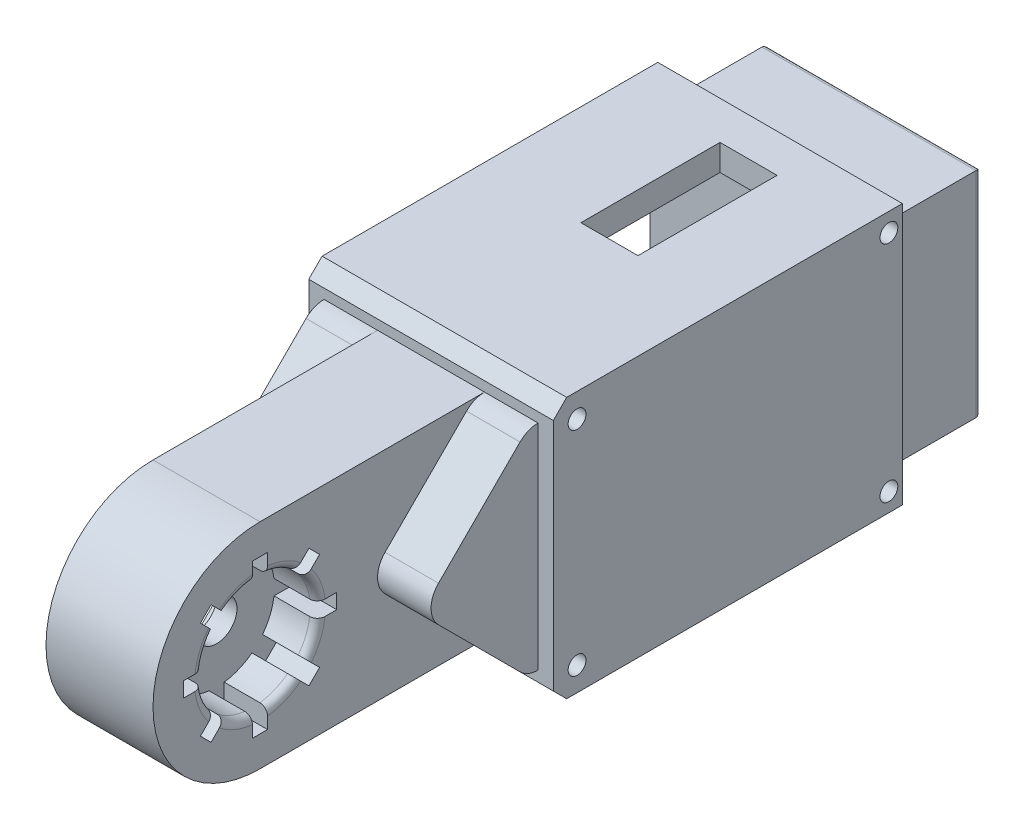
SolidWorks part; units mm, degrees
ref_plane "Front Plane" through (0, 0, 0) normal (0, 0, 1) x (1, 0, 0)
ref_plane "Top Plane" through (0, 0, 0) normal (0, 1, 0) x (1, 0, 0)
ref_plane "Right Plane" through (0, 0, 0) normal (1, 0, 0) x (0, 0, -1)
sketch "Sketch2" plane through (0, 0, 0) normal (0, 0, 1) x (1, 0, 0)
  line L1 (-21, 21) -> (21, 21)
  line L2 (-21, 21) -> (-21, -21)
  line L3 (-21, -21) -> (21, -21)
  line L4 (21, 21) -> (21, -21)
  line L5 (-21, 21) -> (21, -21) construction
  line L6 (-21, -21) -> (21, 21) construction
  point P0 (0, 0)
  dimension "D1" = 42
  dimension "D2" = 42
extrude "Boss-Extrude1" add sketch "Sketch2" along normal blind 89
ref_plane "Plane1" through (0, 0, 89) normal (0, 0, 1) x (1, 0, 0)
sketch "Sketch3" plane through (0, 0, 89) normal (0, 0, 1) x (1, 0, 0)
  line L0 (21, 21) -> (-21, 21) construction
  line L1 (10.5, -21) -> (-10.5, -21)
  line L2 (10.5, -21) -> (10.5, 21)
  line L3 (10.5, 21) -> (-10.5, 21)
  line L4 (-10.5, -21) -> (-10.5, 21)
  line L5 (10.5, -21) -> (-10.5, 21) construction
  line L6 (10.5, 21) -> (-10.5, -21) construction
  point P0 (0, 0)
  dimension "D1" = 21
ref_plane "Plane4" through (0, 0, 0) normal (0, 0, -1) x (-1, 0, 0)
extrude "Boss-Extrude2" add sketch "Sketch3" along normal blind 42
ref_plane "Plane5" through (-10.5, 0, 0) normal (-1, 0, 0) x (0, 0, 1)
sketch "Sketch8" plane through (-10.5, 0, 0) normal (-1, 0, 0) x (0, 0, 1)
  line L0 (131, 21) -> (131, -21) construction
  line L1 (131, 21) -> (131, -21)
  arc A0 (131, 21) -> (131, -21) centre (131, 0) cw
  dimension "D1" = 21
extrude "Boss-Extrude3" add sketch "Sketch8" against normal blind 21
ref_plane "Plane6" through (-10.5, 0, 0) normal (-1, 0, 0) x (0, 0, 1)
sketch "Sketch9" plane through (-10.5, 0, 0) normal (-1, 0, 0) x (0, 0, 1)
  line L0 (89, 21) -> (89, -21) construction
  line L1 (131, 21) -> (131, -21)
  circle A0 centre (131, 0) radius 11.35
  dimension "D1" = 42
  dimension "D2" = 22.7
extrude "Cut-Extrude2" cut sketch "Sketch9" against normal blind 8.5 contours A0
ref_plane "Plane7" through (10.5, 0, 0) normal (1, 0, 0) x (0, 0, -1)
sketch "Sketch11" plane through (10.5, 0, 0) normal (1, 0, 0) x (0, 0, -1)
  line L0 (-131, 21) -> (-131, -21)
  circle A0 centre (-131, 0) radius 11.35
  dimension "D1" = 22.7
extrude "Cut-Extrude3" cut sketch "Sketch11" against normal blind 8.5 contours A0
ref_plane "Plane8" through (-2, 0, 0) normal (-1, 0, 0) x (0, 0, 1)
sketch "Sketch12" plane through (-2, 0, 0) normal (-1, 0, 0) x (0, 0, 1)
  circle A0 centre (131, 0) radius 3.975
  dimension "D1" = 7.95
extrude "Cut-Extrude4" cut sketch "Sketch12" against normal through all
ref_plane "Plane10" through (-2, 0, 0) normal (-1, 0, 0) x (0, 0, 1)
ref_plane "Plane11" through (-10.5, 0, 0) normal (-1, 0, 0) x (0, 0, 1)
sketch "Sketch20" plane through (-10.5, 0, 0) normal (-1, 0, 0) x (0, 0, 1)
  line L0 (131, 0) -> (110, 0)
  line L1 (110, 0) -> (110, 21)
  line L2 (110, 0) -> (110, -21)
  line L4 (110, 21) -> (89, 21)
  line L6 (110, -21) -> (89, -21)
  line L7 (89, 21) -> (110, 0)
  line L8 (89, -21) -> (110, 0)
  line L9 (89, 21) -> (89, -21)
  circle A0 centre (131, 0) radius 11.35
  dimension "D1" = 21
extrude "Boss-Extrude4" add sketch "Sketch20" along normal blind 10.5 and the other way blind 31.5 contours L7 L9 L8 region at (-10.5, 0, 96)
fillet "Fillet1" radius 5 1 edges at (15.75, 0, 110)
fillet "Fillet2" radius 5 1 edges at (-15.75, 0, 110)
fillet "Fillet3" radius 5 1 edges at (-15.75, -21, 89)
fillet "Fillet4" radius 5 1 edges at (-15.75, 21, 89)
fillet "Fillet5" radius 5 1 edges at (15.75, -21, 89)
fillet "Fillet6" radius 5 1 edges at (15.75, 21, 89)
fillet "Fillet7" radius 1.5 1 edges at (-10.5, 0, 142.35)
fillet "Fillet8" radius 1.5 1 edges at (10.5, 0, 119.65)
sketch "Sketch21" plane through (-10.5, 0, 0) normal (-1, 0, 0) x (0, 0, 1)
  line L1 (129.5207, 10.6415) -> (132.4793, 10.6415)
  line L2 (129.5207, 10.6415) -> (129.5207, 15.0585)
  line L3 (129.5207, 15.0585) -> (132.4793, 15.0585)
  line L4 (132.4793, 10.6415) -> (132.4793, 15.0585)
  line L5 (129.5207, 10.6415) -> (132.4793, 15.0585) construction
  line L6 (129.5207, 15.0585) -> (132.4793, 10.6415) construction
  circle A0 centre (131, 0) radius 12.85 construction
  point P0 (131, 12.85)
  dimension "D1" = 4.417
extrude "Cut-Extrude5" cut sketch "Sketch21" against normal blind 8.5
pattern_circular "CirPattern2" count 8 over 360 about axis through (-9, 0, 131) along (-1, 0, 0) of "Cut-Extrude5"
ref_plane "Plane12" through (0, 21, 0) normal (0, 1, 0) x (1, 0, 0)
ref_plane "Plane13" through (10.5, 0, 0) normal (1, 0, 0) x (0, 0, -1)
ref_plane "Plane14" through (0, 0, 0) normal (1, 0, 0) x (0, 0, -1)
mirror "Mirror1" about plane through (0, 0, 0) normal (1, 0, 0) of "CirPattern2"
ref_plane "Plane15" through (21, 0, 0) normal (1, 0, 0) x (0, 0, -1)
sketch "Sketch24" plane through (21, 0, 0) normal (1, 0, 0) x (0, 0, -1)
  line L1 (-86.9289, 21) -> (0, 21)
  line L2 (-86.9289, 21) -> (-86.9289, 25.5452)
  line L3 (-86.9289, 25.5452) -> (0, 25.5452)
  line L4 (0, 21) -> (0, 25.5452)
  line L5 (-86.9289, -21) -> (0, -21)
  line L6 (-86.9289, -21) -> (-86.9289, -25.6891)
  line L7 (-86.9289, -25.6891) -> (0, -25.6891)
  line L8 (0, -21) -> (0, -25.6891)
extrude "Boss-Extrude6" add sketch "Sketch24" against normal blind 42
sketch "Sketch25" plane through (21, 0, 0) normal (1, 0, 0) x (0, 0, -1)
  line L0 (-18.4289, -25.6891) -> (-18.4289, 25.5452)
  line L1 (-86.9289, 25.5452) -> (-18.4289, 25.5452)
  line L2 (-86.9289, 25.5452) -> (-86.9289, -25.6891)
  line L3 (-86.9289, -25.6891) -> (-18.4289, -25.6891)
  dimension "D1" = 68.5
extrude "Boss-Extrude7" add sketch "Sketch25" along normal blind 3
ref_plane "Plane18" through (0, 0, 0) normal (0, 0, -1) x (-1, 0, 0)
ref_plane "Plane19" through (-21, 0, 0) normal (-1, 0, 0) x (0, 0, 1)
sketch "Sketch28" plane through (-21, 0, 0) normal (-1, 0, 0) x (0, 0, 1)
  line L0 (86.9289, -25.6891) -> (0, -25.6891) construction
  line L1 (86.9289, 25.5452) -> (18.4289, 25.5452)
  line L2 (86.9289, 25.5452) -> (86.9289, -25.6891)
  line L3 (86.9289, -25.6891) -> (18.4289, -25.6891)
  line L4 (18.4289, 25.5452) -> (18.4289, -25.6891)
  dimension "D1" = 68.5
extrude "Boss-Extrude8" add sketch "Sketch28" along normal blind 3
ref_plane "Plane20" through (-24, 0, 0) normal (-1, 0, 0) x (0, 0, 1)
sketch "Sketch30" plane through (-24, 0, 0) normal (-1, 0, 0) x (0, 0, 1)
  line L1 (81.9289, 20.4302) -> (19.9289, 20.4302)
  line L2 (81.9289, 20.4302) -> (81.9289, -20.5741)
  line L3 (81.9289, -20.5741) -> (19.9289, -20.5741)
  line L4 (19.9289, 20.4302) -> (19.9289, -20.5741)
  line L5 (81.9289, 20.4302) -> (19.9289, -20.5741) construction
  line L6 (81.9289, -20.5741) -> (19.9289, 20.4302) construction
  line L8 (86.9289, 25.5452) -> (18.4289, 25.5452) construction
  line L9 (18.4289, -25.6891) -> (86.9289, -25.6891) construction
  line L10 (86.9289, -21) -> (86.9289, 21) construction
  point P0 (50.9289, -0.0719)
  dimension "D1" = 5.115
  dimension "D2" = 5.115
  dimension "D3" = 62
  dimension "D4" = 5
extrude "Cut-Extrude6" cut sketch "Sketch30" against normal blind 45
ref_plane "Plane21" through (21, 0, 0) normal (1, 0, 0) x (0, 0, -1)
sketch "Sketch31" plane through (21, 0, 0) normal (1, 0, 0) x (0, 0, -1)
  line L0 (0, -25.6891) -> (0, 25.5452) construction
  line L1 (-18.4289, -25.6891) -> (0, -25.6891)
  line L2 (-18.4289, -25.6891) -> (-18.4289, -21.0741)
  line L3 (-18.4289, -21.0741) -> (0, -21.0741)
  line L4 (0, -25.6891) -> (0, -21.0741)
  line L6 (-18.4289, 25.5452) -> (0, 25.5452)
  line L7 (-18.4289, 25.5452) -> (-18.4289, 20.9302)
  line L8 (-18.4289, 20.9302) -> (0, 20.9302)
  line L9 (0, 25.5452) -> (0, 20.9302)
  dimension "D1" = 4.615
  dimension "D2" = 4.615
extrude "Cut-Extrude7" cut sketch "Sketch31" against normal through all
chamfer "Chamfer1" distance 1.5 angle 45 4 edges at (0, 20.9302, 18.4289) (21, -0.0719, 18.4289) (0, -21.0741, 18.4289) (-21, -0.0719, 18.4289)
ref_plane "Plane22" through (0, 0, 0) normal (0, 0, -1) x (-1, 0, 0)
sketch "Sketch32" plane through (0, 0, 0) normal (0, 0, -1) x (-1, 0, 0)
  line L1 (15, 15) -> (-15, 15)
  line L2 (15, 15) -> (15, -15)
  line L3 (15, -15) -> (-15, -15)
  line L4 (-15, 15) -> (-15, -15)
  line L5 (15, 15) -> (-15, -15) construction
  line L6 (15, -15) -> (-15, 15) construction
  point P0 (0, 0)
  dimension "D1" = 30
  dimension "D2" = 30
extrude "Cut-Extrude8" cut sketch "Sketch32" against normal blind 16.8
ref_plane "Plane23" through (0, 0, 19.9289) normal (0, 0, 1) x (1, 0, 0)
sketch "Sketch33" plane through (0, 0, 19.9289) normal (0, 0, 1) x (1, 0, 0)
  circle A0 centre (0, 0) radius 5
  dimension "D1" = 10
extrude "Cut-Extrude9" cut sketch "Sketch33" against normal blind 16.8
ref_plane "Plane24" through (-21, 0, 0) normal (-1, 0, 0) x (0, 0, 1)
sketch "Sketch34" plane through (-24, 0, 0) normal (-1, 0, 0) x (0, 0, 1)
  line L0 (86.9289, -0.0719) -> (103.6427, -0.0719) construction
  line L2 (88.3304, -21.6696) -> (88.3304, -28.2221)
  line L3 (88.3304, -28.2221) -> (81.7779, -28.2221)
  line L4 (81.7779, -28.2221) -> (88.3304, -21.6696)
  line L5 (86.9289, -25.6891) -> (86.9289, 25.5452) construction
  line L6 (88.3304, 28.0782) -> (81.7779, 28.0782)
  line L7 (88.3304, 21.5257) -> (88.3304, 28.0782)
  line L8 (81.7779, 28.0782) -> (88.3304, 21.5257)
extrude "Cut-Extrude10" cut sketch "Sketch34" against normal through all
chamfer "Chamfer2" distance 6 angle 45 1 edges at (-1.5, 20.4302, 81.9289)
chamfer "Chamfer3" distance 6 angle 45 1 edges at (-1.5, -20.5741, 81.9289)
chamfer "Chamfer4" distance 6 angle 45 1 edges at (-1.5, 20.4302, 19.9289)
chamfer "Chamfer5" distance 6 angle 45 1 edges at (-1.5, -20.5741, 19.9289)
sketch "Sketch35" plane through (-24, 0, 0) normal (-1, 0, 0) x (0, 0, 1)
  line L0 (78.9289, -17.5741) -> (85.6199, -24.3801) construction
  line L1 (82.2744, 20.8332) -> (85.6199, 24.2362) construction
  line L2 (81.9289, -14.5741) -> (75.9289, -20.5741) construction
  line L3 (84.3109, -25.6891) -> (86.9289, -23.0711) construction
  line L4 (78.9289, 17.4302) -> (85.6199, 24.2362) construction
  line L5 (75.9289, 20.4302) -> (81.9289, 14.4302) construction
  line L6 (86.9289, 22.9272) -> (84.3109, 25.5452) construction
  line L7 (18.4289, 25.5452) -> (21.0741, 21.9048) construction
  line L9 (18.4289, -25.6891) -> (21.074, -22.0485) construction
  line L10 (18.4289, 25.5452) -> (18.4289, -25.6891) construction
  circle A0 centre (21.0741, 21.9048) radius 1.75
  circle A1 centre (82.2744, 20.8332) radius 1.75
  circle A2 centre (82.2744, -20.9771) radius 1.75
  circle A3 centre (21.074, -22.0485) radius 1.75
  dimension "D5" = 3.5
  dimension "D1" = 36.003
  dimension "D2" = 36
  dimension "D3" = 4.5
  dimension "D4" = 4.5
extrude "Cut-Extrude11" cut sketch "Sketch35" against normal through all
ref_plane "Plane26" through (0, -25.6891, 0) normal (0, -1, 0) x (-1, 0, 0)
sketch "Sketch38" plane through (0, -25.6891, 0) normal (0, -1, 0) x (-1, 0, 0)
  line L0 (-24, -18.4289) -> (24, -18.4289) construction
  line L1 (4.2922, -53.2289) -> (-6.9078, -53.2289)
  line L2 (4.2922, -53.2289) -> (4.2922, -25.9289)
  line L3 (4.2922, -25.9289) -> (-6.9078, -25.9289)
  line L4 (-6.9078, -53.2289) -> (-6.9078, -25.9289)
  dimension "D1" = 7.5
  dimension "D2" = 27.3
  dimension "D3" = 11.2
extrude "Cut-Extrude12" cut sketch "Sketch38" against normal through all
fillet "Fillet9" radius 1 4 edges at (21, -0.0719, 0) (0, 20.9302, 0) (0, -21.0741, 0) (-21, -0.0719, 0)
fillet "Fillet10" radius 1 4 edges at (0, 15, 0) (15, 0, 0) (0, -15, 0) (-15, 0, 0)
